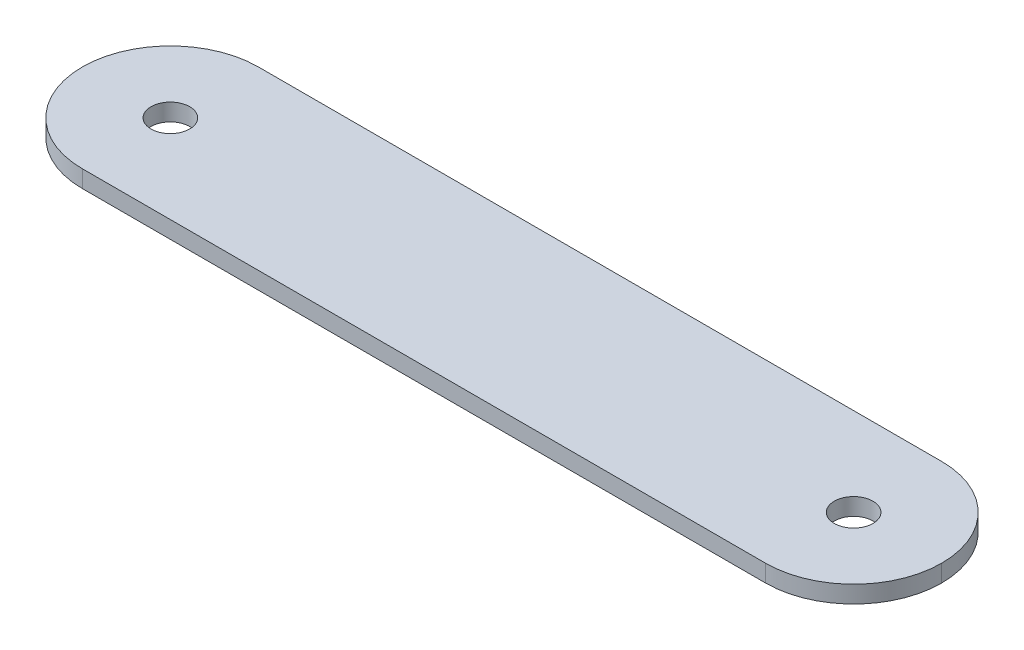
SolidWorks part; units mm, degrees
ref_plane "Front Plane" through (0, 0, 0) normal (0, 0, 1) x (1, 0, 0)
ref_plane "Top Plane" through (0, 0, 0) normal (0, 1, 0) x (1, 0, 0)
ref_plane "Right Plane" through (0, 0, 0) normal (1, 0, 0) x (0, 0, -1)
sketch "Sketch1" plane through (0, 0, 0) normal (0, 1, 0) x (1, 0, 0)
  line L0 (0, 10.25) -> (100, 10.25) construction
  line L1 (0, 0) -> (100, 0)
  line L2 (0, 0) -> (0, 20.5)
  line L3 (0, 20.5) -> (100, 20.5)
  line L4 (100, 0) -> (100, 20.5)
  line L5 (50, 20.5) -> (50, 0) construction
  circle A0 centre (10.25, 10.25) radius 2.25
  circle A9 centre (89.75, 10.25) radius 2.25
  dimension "D3" = 4.5
  dimension "D1" = 100
  dimension "D2" = 20.5
  dimension "D5" = 10.25
extrude "Boss-Extrude1" add sketch "Sketch1" along normal blind 2
fillet "Fillet1" radius 10.25 4 edges at (0, 1, 0) (0, 1, -20.5) (100, 1, -20.5) (100, 1, 0)
